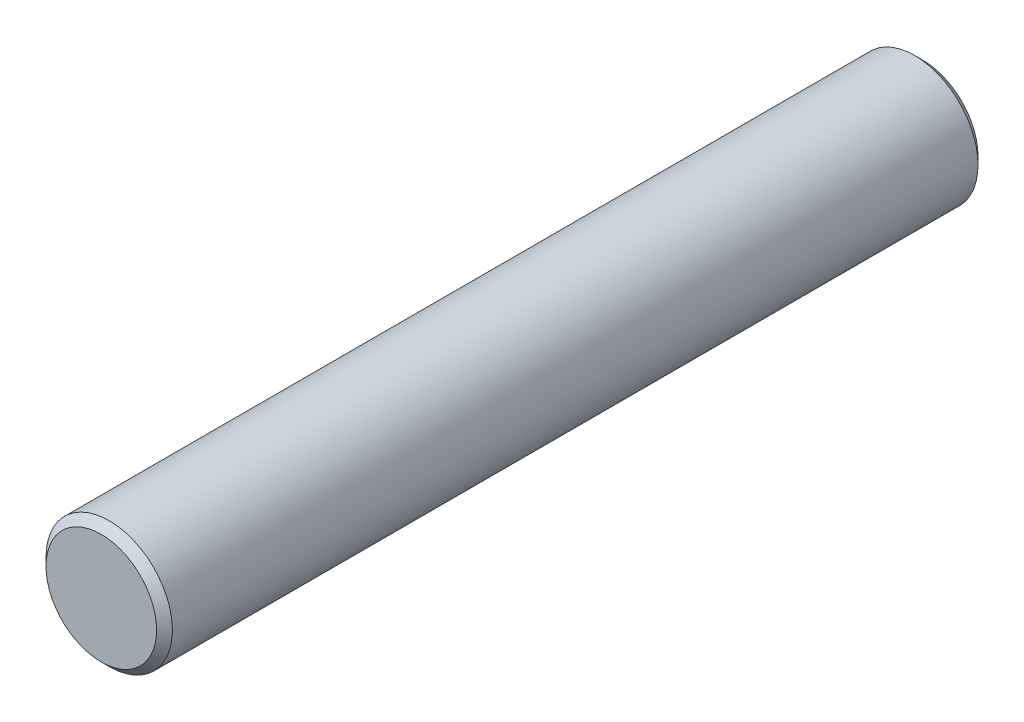
SolidWorks part; units mm, degrees
ref_plane "Спереди" through (0, 0, 0) normal (0, 0, 1) x (1, 0, 0)
ref_plane "Сверху" through (0, 0, 0) normal (0, 1, 0) x (1, 0, 0)
ref_plane "Справа" through (0, 0, 0) normal (1, 0, 0) x (0, 0, -1)
sketch "Эскиз1" plane through (0, 0, 0) normal (0, 0, 1) x (1, 0, 0)
  circle A0 centre (0, 0) radius 4
extrude "Вытянуть1" add sketch "Эскиз1" along normal blind 52
cosmetic thread "Условное изображение резьбы1" parameters "D1"=20, "D2"=7.5
cosmetic thread "Условное изображение резьбы2" parameters "D1"=20, "D2"=7.5
cosmetic thread "Условное изображение резьбы3" parameters "D1"=20, "D2"=7.5
chamfer "Фаска1" distance 0.5 angle 45 2 edges at (4, 0, 52) (4, 0, 0)
